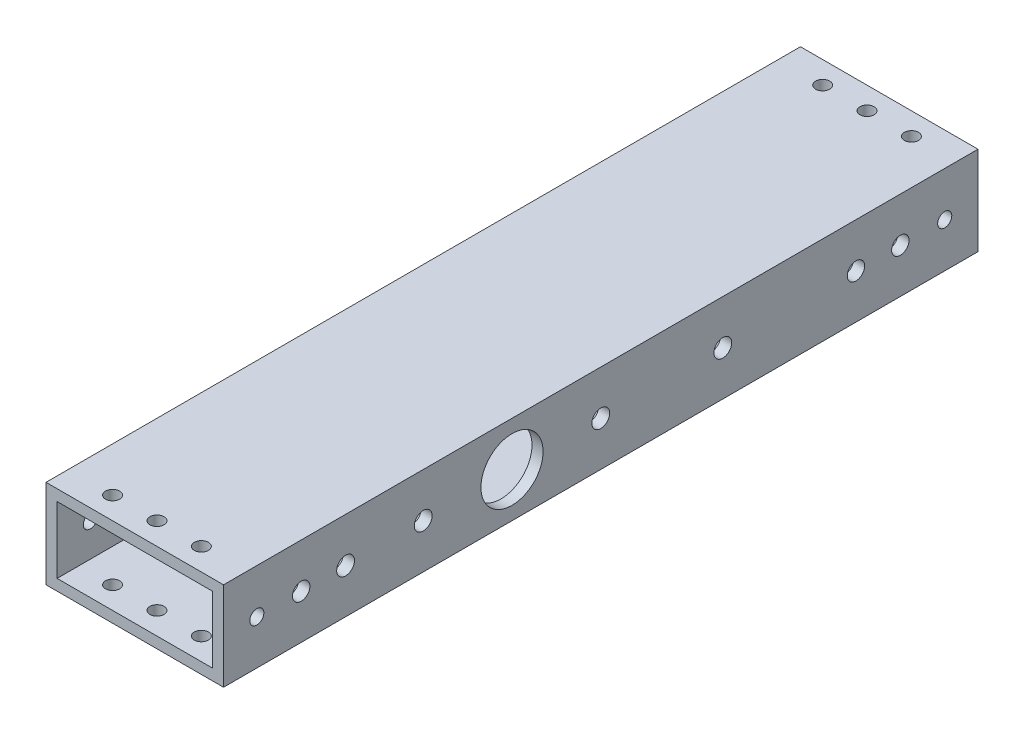
SolidWorks part; units mm, degrees
material "6061-T6 (SS)"
ref_plane "Front Plane" through (0, 0, 0) normal (0, 0, 1) x (1, 0, 0)
ref_plane "Top Plane" through (0, 0, 0) normal (0, 1, 0) x (1, 0, 0)
ref_plane "Right Plane" through (0, 0, 0) normal (1, 0, 0) x (0, 0, -1)
sketch "Sketch1" plane through (0, 0, 0) normal (0, 0, 1) x (1, 0, 0)
  line L0 (-22.225, 9.525) -> (22.225, 9.525)
  line L1 (-25.4, -12.7) -> (25.4, -12.7)
  line L2 (-25.4, -12.7) -> (-25.4, 12.7)
  line L3 (-25.4, 12.7) -> (25.4, 12.7)
  line L4 (25.4, -12.7) -> (25.4, 12.7)
  line L5 (-25.4, -12.7) -> (25.4, 12.7) construction
  line L6 (-25.4, 12.7) -> (25.4, -12.7) construction
  line L7 (22.225, -9.525) -> (22.225, 9.525)
  line L8 (-22.225, -9.525) -> (22.225, -9.525)
  line L9 (-22.225, -9.525) -> (-22.225, 9.525)
  point P0 (0, 0)
  dimension "D1" = 50.8
  dimension "D2" = 25.4
  dimension "D3" = 3.175
extrude "Boss-Extrude1" add sketch "Sketch1" along normal mid plane 215.9
sketch "Sketch2" plane through (25.4, 0, 0) normal (1, 0, 0) x (0, 0, -1)
  line L0 (-107.95, -12.7) -> (-107.95, 12.7) construction
  line L1 (0, 12.7) -> (0, -12.7) construction
  line L2 (-107.95, 12.7) -> (107.95, 12.7) construction
  line L3 (-107.95, -12.7) -> (107.95, -12.7) construction
  circle A0 centre (-98.425, 0) radius 2.0193
  circle A1 centre (98.425, 0) radius 2.0193
  circle A2 centre (-85.725, 0) radius 2.4892
  circle A3 centre (-73.025, 0) radius 2.4892
  circle A4 centre (73.025, 0) radius 2.4892
  circle A5 centre (85.725, 0) radius 2.4892
  dimension "D2" = 4.0386
  dimension "D5" = 4.9784
  dimension "D1" = 9.525
  dimension "D3" = 12.7
  dimension "D4" = 12.7
extrude "Cut-Extrude1" cut sketch "Sketch2" against normal through all
sketch "Sketch3" plane through (0, 12.7, 0) normal (0, 1, 0) x (1, 0, 0)
  line L0 (-25.4, 0) -> (25.4, 0) construction
  line L1 (-25.4, -107.95) -> (-25.4, 107.95) construction
  line L2 (25.4, -107.95) -> (25.4, 107.95) construction
  line L3 (25.4, -107.95) -> (-25.4, -107.95) construction
  circle A0 centre (-12.7, -101.6) radius 2.0193
  circle A1 centre (0, -101.6) radius 2.0193
  circle A2 centre (12.7, -101.6) radius 2.0193
  circle A3 centre (12.7, 101.6) radius 2.0193
  circle A4 centre (0, 101.6) radius 2.0193
  circle A5 centre (-12.7, 101.6) radius 2.0193
  dimension "D1" = 4.0386
  dimension "D2" = 12.7
  dimension "D3" = 12.7
  dimension "D4" = 6.35
extrude "Cut-Extrude2" cut sketch "Sketch3" against normal through all
sketch "Sketch4" plane through (25.4, 0, 0) normal (1, 0, 0) x (0, 0, -1)
  line L0 (-25.4, 0) -> (-73.025, 0) construction
  line L1 (-16.51, 0) -> (-34.29, 0) construction
  line L8 (-25.4, 0) -> (34.925, 0) construction
  line L9 (0, 12.7) -> (0, -12.7) construction
  line L10 (-107.95, 12.7) -> (107.95, 12.7) construction
  line L11 (-107.95, -12.7) -> (107.95, -12.7) construction
  circle A0 centre (-25.4, 0) radius 8.89
  circle A5 centre (-73.025, 0) radius 2.5527
  circle A7 centre (-73.025, 0) radius 2.4892 construction
  circle A9 centre (34.925, 0) radius 2.5527
  circle A10 centre (0, 0) radius 2.5527
  circle A11 centre (-50.8, 0) radius 2.5527
  dimension "D2" = 17.78
  dimension "D3" = 25.4
  dimension "D1" = 60.325
  dimension "D4" = 5.1054
  dimension "D5" = 25.4
  dimension "D6" = 25.4
extrude "Cut-Extrude3" cut sketch "Sketch4" against normal through all contours A0 | A5 | A9 | A11 | A10
sketch "Sketch5" plane through (0, -12.7, 0) normal (0, -1, 0) x (1, 0, 0)
  line L0 (-25.4, 107.95) -> (-25.4, -107.95) construction
  line L1 (-25.4, 107.95) -> (25.4, 107.95) construction
  line L2 (-16.51, -12.7) -> (-3.81, -12.7) construction
  line L3 (-16.51, -12.7) -> (-16.51, 0) construction
  circle A0 centre (-3.81, 63.5) radius 2.5527
  circle A1 centre (-16.51, 63.5) radius 2.5527
  circle A2 centre (-16.51, 50.8) radius 2.5527
  circle A3 centre (-3.81, 50.8) radius 2.5527
  circle A4 centre (-16.51, -12.7) radius 2.5527
  circle A5 centre (-3.81, -12.7) radius 2.5527
  circle A6 centre (-3.81, 0) radius 2.5527
  circle A7 centre (-16.51, 0) radius 2.5527
  dimension "D3" = 5.1054
  dimension "D4" = 8.89
  dimension "D7" = 12.7
  dimension "D12" = 50.8
  dimension "D5" = 44.45
  dimension "D6" = 12.7
  dimension "D10" = 12.7
  dimension "D11" = 12.7
  dimension "D1" = 2
  dimension "D2" = 2
  dimension "D8" = 2
  dimension "D9" = 2
extrude "Cut-Extrude4" cut sketch "Sketch5" against normal up to next
